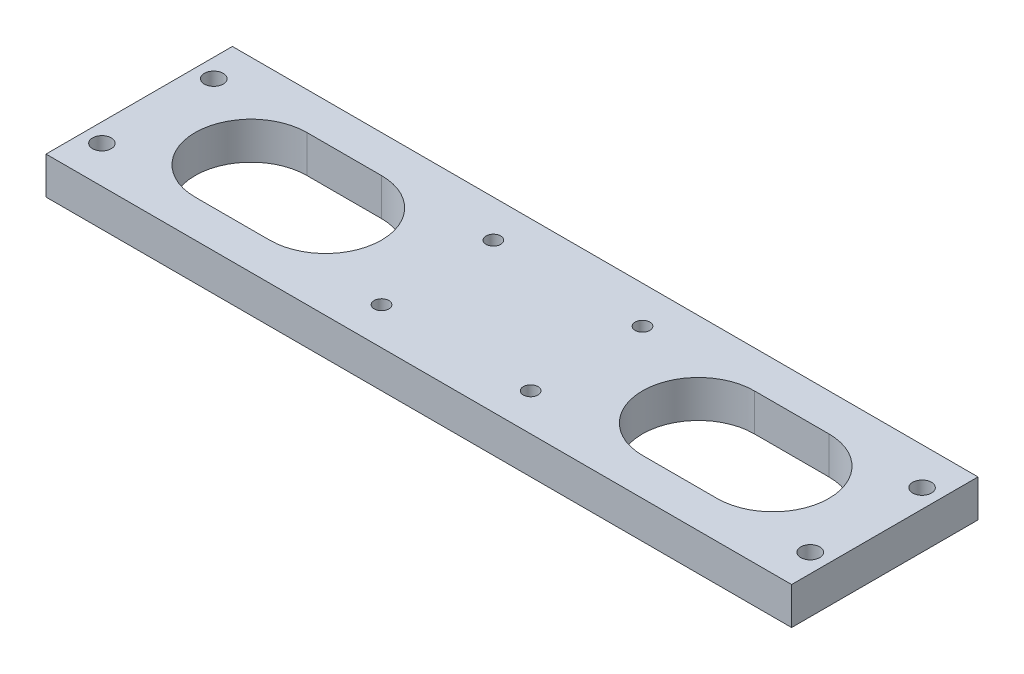
SolidWorks part; units mm, degrees
material "6061 Alloy"
ref_plane "Front Plane" through (0, 0, 0) normal (0, 0, 1) x (1, 0, 0)
ref_plane "Top Plane" through (0, 0, 0) normal (0, 1, 0) x (1, 0, 0)
ref_plane "Right Plane" through (0, 0, 0) normal (1, 0, 0) x (0, 0, -1)
sketch "Sketch1" plane through (0, 0, 0) normal (0, 1, 0) x (1, 0, 0)
  line L1 (-63.5, -15.875) -> (63.5, -15.875)
  line L2 (-63.5, -15.875) -> (-63.5, 15.875)
  line L3 (-63.5, 15.875) -> (63.5, 15.875)
  line L4 (63.5, -15.875) -> (63.5, 15.875)
  line L5 (-63.5, -15.875) -> (63.5, 15.875) construction
  line L6 (-63.5, 15.875) -> (63.5, -15.875) construction
  point P0 (0, 0)
  dimension "D1" = 127
  dimension "D2" = 31.75
extrude "Boss-Extrude1" add sketch "Sketch1" along normal mid plane 6.35
sketch "Sketch2" plane through (0, -3.175, 0) normal (0, -1, 0) x (1, 0, 0)
  point P2 (-60.325, -9.525)
  point P4 (60.325, -9.525)
  point P6 (60.325, 9.525)
  point P7 (-60.325, 9.525)
hole_wizard "CSK for M3 Flat Head Machine Screw1" positions "Sketch3" profile "Sketch5" countersink size "M3" standard "ANSI Metric"
sketch "Sketch3" plane through (0, -3.175, 0) normal (0, -1, 0) x (-1, 0, 0)
  point P13 (60.325, 9.525)
  point P16 (60.325, -9.525)
  point P22 (-60.325, -9.525)
  point P27 (-60.325, 9.525)
sketch "Sketch5" plane through (-60.325, -3.175, -9.525) normal (1, 0, 0) x (0, 0, -1)
  line L0 (0, 0) -> (0, 13.6614)
  line L1 (0, 13.6614) -> (1.6, 12.7)
  line L2 (1.6, 12.7) -> (1.6, 1.55)
  line L3 (1.6, 1.55) -> (3.15, 0)
  line L5 (3.15, 0) -> (0, 0)
  line L6 (-1.6, 1.55) -> (-3.15, 0) construction
  line L10 (0, 13.6614) -> (-1.6, 12.7) construction
  line L11 (0, -6.35) -> (0, 107.95) construction
  dimension "Hole Dia." = 3.2
  dimension "Hole Depth" = 12.7
  dimension "Near C'Sink Dia." = 6.3
  dimension "Near C'Sink Angle" = 90
  dimension "Drill Angle" = 118
sketch "Sketch6" plane through (0, 3.175, 0) normal (0, 1, 0) x (1, 0, 0)
  line L1 (-12.7, -9.525) -> (12.7, -9.525)
  line L2 (-12.7, -9.525) -> (-12.7, 9.525)
  line L3 (-12.7, 9.525) -> (12.7, 9.525)
  line L4 (12.7, -9.525) -> (12.7, 9.525)
  line L5 (-12.7, -9.525) -> (12.7, 9.525) construction
  line L6 (-12.7, 9.525) -> (12.7, -9.525) construction
  point P0 (0, 0)
  point P7 (-12.7, 9.525)
  point P8 (12.7, 9.525)
  point P9 (12.7, -9.525)
  point P10 (-12.7, -9.525)
  dimension "D1" = 25.4
  dimension "D2" = 19.05
hole_wizard "M3x0.5 Tapped Hole1" positions "Sketch7" profile "Sketch9" tap size "M3x0.5" standard "ANSI Metric" end condition through all
sketch "Sketch7" plane through (0, 3.175, 0) normal (0, 1, 0) x (1, 0, 0)
  point P0 (-12.7, 9.525)
  point P3 (12.7, 9.525)
  point P6 (12.7, -9.525)
  point P9 (-12.7, -9.525)
cosmetic thread "Hole Thread1" parameters "D2"=3
cosmetic thread "Hole Thread2" parameters "D2"=3
cosmetic thread "Hole Thread3" parameters "D2"=3
cosmetic thread "Hole Thread4" parameters "D2"=3
sketch "Sketch9" plane through (-12.7, 3.175, -9.525) normal (1, 0, 0) x (0, 0, 1)
  line L0 (0, 0) -> (0, 6.35)
  line L1 (0, 6.35) -> (1.25, 6.35)
  line L2 (1.25, 6.35) -> (1.25, 0)
  line L5 (1.25, 0) -> (0, 0)
  line L11 (0, -6.35) -> (0, 107.95) construction
  dimension "Thru Tap Drill Dia." = 2.5
  dimension "Thru Tap Drill Depth" = 6.35
sketch "Sketch10" plane through (0, 3.175, 0) normal (0, 1, 0) x (1, 0, 0)
  line L0 (-44.45, 0) -> (-31.75, 0) construction
  line L1 (-44.45, 9.525) -> (-31.75, 9.525)
  line L2 (-44.45, -9.525) -> (-31.75, -9.525)
  line L3 (44.45, 0) -> (31.75, 0) construction
  line L4 (44.45, -9.525) -> (31.75, -9.525)
  line L5 (44.45, 9.525) -> (31.75, 9.525)
  line L6 (-38.1, 0) -> (38.1, 0) construction
  line L7 (0, -3.4925) -> (0, 3.4925) construction
  arc A0 (-44.45, 9.525) -> (-44.45, -9.525) centre (-44.45, 0) ccw
  arc A1 (-31.75, -9.525) -> (-31.75, 9.525) centre (-31.75, 0) ccw
  arc A2 (44.45, -9.525) -> (44.45, 9.525) centre (44.45, 0) ccw
  arc A3 (31.75, 9.525) -> (31.75, -9.525) centre (31.75, 0) ccw
  point P3 (-38.1, 0)
  point P8 (38.1, 0)
  point P20 (0, 0)
  dimension "D1" = 76.2
  dimension "D2" = 19.05
  dimension "D3" = 12.7
extrude "Cut-Extrude1" cut sketch "Sketch10" against normal through all
